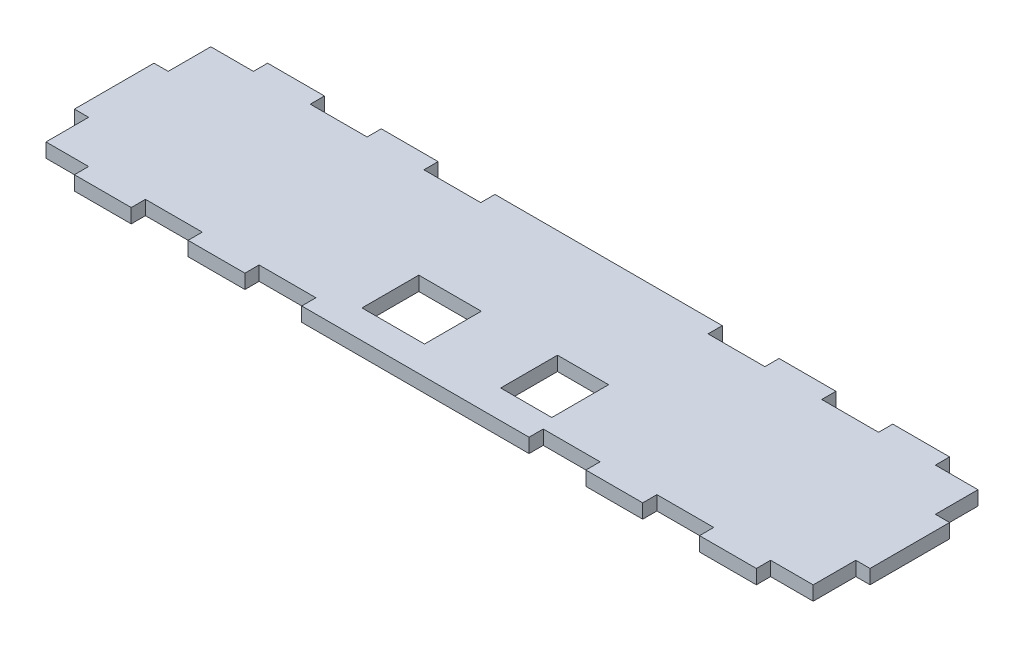
SolidWorks part; units mm, degrees
material "Acrylic (Medium-high impact)"
ref_plane "Front Plane" through (0, 0, 0) normal (0, 0, 1) x (1, 0, 0)
ref_plane "Top Plane" through (0, 0, 0) normal (0, 1, 0) x (1, 0, 0)
ref_plane "Right Plane" through (0, 0, 0) normal (1, 0, 0) x (0, 0, -1)
sketch "Sketch1" plane through (0, 0, 0) normal (0, 1, 0) x (1, 0, 0)
  line L1 (0, 0) -> (171.45, 0)
  line L2 (0, 0) -> (0, 36.83)
  line L3 (0, 36.83) -> (171.45, 36.83)
  line L4 (171.45, 0) -> (171.45, 36.83)
  dimension "D1" = 36.83
  dimension "D2" = 171.45
extrude "Boss-Extrude1" add sketch "Sketch1" along normal blind 3.175
sketch "Sketch2" plane through (0, 3.175, 0) normal (0, 1, 0) x (1, 0, 0)
  line L0 (85.725, 0) -> (85.725, -16.8439) construction
  line L1 (0, 0) -> (171.45, 0) construction
  line L2 (22.225, 0) -> (34.925, 0)
  line L3 (0, 0) -> (-3.175, 0)
  line L4 (0, 0) -> (0, -3.175)
  line L5 (0, -3.175) -> (-3.175, -3.175)
  line L6 (-3.175, 0) -> (-3.175, -3.175)
  line L7 (-3.175, 0) -> (9.525, 0)
  line L8 (-3.175, 0) -> (-3.175, -3.175)
  line L9 (-3.175, -3.175) -> (9.525, -3.175)
  line L10 (9.525, 0) -> (9.525, -3.175)
  line L11 (22.225, 0) -> (22.225, -3.175)
  line L12 (22.225, -3.175) -> (34.925, -3.175)
  line L13 (34.925, 0) -> (34.925, -3.175)
  line L14 (47.625, 0) -> (60.325, 0)
  line L15 (47.625, 0) -> (47.625, -3.175)
  line L16 (47.625, -3.175) -> (60.325, -3.175)
  line L17 (60.325, 0) -> (60.325, -3.175)
  line L18 (-3.175, -3.175) -> (174.625, -3.175)
  line L19 (85.725, -3.175) -> (85.725, 0)
  line L20 (174.625, 0) -> (-3.175, 0)
  line L21 (111.125, 0) -> (111.125, -3.175)
  line L22 (123.825, -3.175) -> (111.125, -3.175)
  line L23 (123.825, 0) -> (123.825, -3.175)
  line L24 (123.825, 0) -> (111.125, 0)
  line L25 (136.525, 0) -> (136.525, -3.175)
  line L26 (149.225, -3.175) -> (136.525, -3.175)
  line L27 (149.225, 0) -> (149.225, -3.175)
  line L28 (161.925, 0) -> (161.925, -3.175)
  line L29 (174.625, -3.175) -> (161.925, -3.175)
  line L30 (174.625, 0) -> (174.625, -3.175)
  line L31 (174.625, 0) -> (161.925, 0)
  line L32 (174.625, 0) -> (174.625, -3.175)
  line L33 (171.45, -3.175) -> (174.625, -3.175)
  line L34 (171.45, 0) -> (171.45, -3.175)
  line L35 (171.45, 0) -> (174.625, 0)
  line L36 (149.225, 0) -> (136.525, 0)
  line M3 (0, 0) -> (171.45, 0)
  dimension "D1" = 3.175
  dimension "D2" = 12.7
  dimension "D3" = 3
extrude "Boss-Extrude2" add sketch "Sketch2" against normal blind 3.175 contours L10 L18 L11 M3 | L13 L18 L15 M3 | L18 L19 L17 M3 | L21 L19 L18 M3 | L25 L23 L18 M3 | L28 L27 L18 M3 region at (15.875, 3.175, 1.5875) region at (41.275, 3.175, 1.5875) region at (73.025, 3.175, 1.5875) region at (98.425, 3.175, 1.5875) region at (130.175, 3.175, 1.5875) region at (155.575, 3.175, 1.5875)
sketch "Sketch3" plane through (0, 3.175, 0) normal (0, 1, 0) x (1, 0, 0)
  line L0 (85.725, -3.175) -> (85.725, 3.175) construction
  line L1 (60.325, -3.175) -> (111.125, -3.175) construction
  line L2 (0, 3.175) -> (171.45, 3.175) construction
  line L3 (0, 36.83) -> (0, 0) construction
  line L4 (171.45, 0) -> (171.45, 36.83) construction
  line L6 (60.325, 0) -> (67.437, 0)
  line L7 (60.325, 0) -> (60.325, 25.654)
  line L8 (60.325, 25.654) -> (67.437, 25.654)
  line L9 (67.437, 0) -> (67.437, 25.654)
  line L10 (111.125, 0) -> (109.855, 0)
  line L11 (111.125, 0) -> (111.125, 29.21)
  line L12 (111.125, 29.21) -> (109.855, 29.21)
  line L13 (109.855, 0) -> (109.855, 29.21)
  line L14 (67.437, 3.175) -> (109.855, 3.175)
  line L15 (67.437, 3.175) -> (67.437, 15.875)
  line L16 (67.437, 15.875) -> (109.855, 15.875)
  line L17 (109.855, 3.175) -> (109.855, 15.875)
  dimension "D1" = 6.35
  dimension "D2" = 7.112
  dimension "D3" = 1.27
  dimension "D4" = 12.7
extrude "Cut-Extrude1" cut sketch "Sketch3" against normal blind 3.175 contours L14 L17 L16 L15
sketch "Sketch5" plane through (0, 3.175, 0) normal (0, 1, 0) x (1, 0, 0)
  line L0 (67.437, 3.175) -> (109.855, 3.175) construction
  line L1 (67.437, 15.875) -> (81.407, 15.875)
  line L2 (67.437, 15.875) -> (67.437, 3.175)
  line L3 (67.437, 3.175) -> (81.407, 3.175)
  line L4 (81.407, 15.875) -> (81.407, 3.175)
  line L5 (67.437, 15.875) -> (109.855, 15.875) construction
  line L6 (109.855, 3.175) -> (98.425, 3.175)
  line L7 (109.855, 3.175) -> (109.855, 15.875)
  line L8 (109.855, 15.875) -> (98.425, 15.875)
  line L9 (98.425, 3.175) -> (98.425, 15.875)
  line L11 (81.407, 15.875) -> (98.425, 15.875)
  line L12 (81.407, 15.875) -> (81.407, 3.175)
  line L13 (81.407, 3.175) -> (98.425, 3.175)
  line L14 (98.425, 15.875) -> (98.425, 3.175)
  line M26 (67.437, 15.875) -> (109.855, 15.875)
  line M28 (109.855, 3.175) -> (67.437, 3.175)
  dimension "D1" = 13.97
  dimension "D2" = 11.43
extrude "Boss-Extrude3" add sketch "Sketch5" against normal blind 3.175 contours L9 L4 M28 M26 region at (89.916, 3.175, -9.525)
sketch "Sketch6" plane through (0, 3.175, 0) normal (0, 1, 0) x (1, 0, 0)
  line L0 (0, 36.83) -> (0, 0) construction
  line L1 (9.525, -3.175) -> (-3.175, -3.175)
  line L2 (9.525, -3.175) -> (9.525, 9.525)
  line L3 (9.525, 9.525) -> (-3.175, 9.525)
  line L4 (-3.175, -3.175) -> (-3.175, 9.525)
  line L5 (161.925, -3.175) -> (174.625, -3.175)
  line L6 (161.925, -3.175) -> (161.925, 9.525)
  line L7 (161.925, 9.525) -> (174.625, 9.525)
  line L8 (174.625, -3.175) -> (174.625, 9.525)
  line L9 (0, 36.83) -> (-3.175, 36.83)
  line L10 (0, 36.83) -> (0, 40.005)
  line L11 (0, 40.005) -> (-3.175, 40.005)
  line L12 (-3.175, 36.83) -> (-3.175, 40.005)
  line L13 (171.45, 36.83) -> (174.625, 36.83)
  line L14 (171.45, 36.83) -> (171.45, 40.005)
  line L15 (171.45, 40.005) -> (174.625, 40.005)
  line L16 (174.625, 36.83) -> (174.625, 40.005)
  line L17 (174.625, 40.005) -> (161.925, 40.005)
  line L18 (174.625, 40.005) -> (174.625, 27.305)
  line L19 (174.625, 27.305) -> (161.925, 27.305)
  line L20 (161.925, 40.005) -> (161.925, 27.305)
  line L21 (-3.175, 40.005) -> (9.525, 40.005)
  line L22 (-3.175, 40.005) -> (-3.175, 27.305)
  line L23 (-3.175, 27.305) -> (9.525, 27.305)
  line L24 (9.525, 40.005) -> (9.525, 27.305)
  line L25 (-3.175, 27.305) -> (0, 27.305)
  line L26 (-3.175, 27.305) -> (-3.175, 9.525)
  line L27 (-3.175, 9.525) -> (0, 9.525)
  line L28 (0, 27.305) -> (0, 9.525)
  line L29 (171.45, 0) -> (171.45, 36.83) construction
  line L30 (174.625, 27.305) -> (171.45, 27.305)
  line L31 (174.625, 27.305) -> (174.625, 9.525)
  line L32 (174.625, 9.525) -> (171.45, 9.525)
  line L33 (171.45, 27.305) -> (171.45, 9.525)
  line M5 (0, 36.83) -> (0, 0)
  line M27 (171.45, 0) -> (171.45, 36.83)
  dimension "D1" = 12.7
  dimension "D2" = 12.7
  dimension "D3" = 12.7
  dimension "D4" = 3.175
  dimension "D5" = 3.175
  dimension "D6" = 12.7
  dimension "D7" = 12.7
extrude "Boss-Extrude4" add sketch "Sketch6" against normal blind 3.175 contours L31 L19 L7 M27 | L23 L26 L3 M5 region at (-1.5875, 3.175, -18.415) region at (173.0375, 3.175, -18.415)
ref_plane "Plane2" through (0, 0, -18.415) normal (0, 0, -1) x (-1, 0, 0)
mirror "Mirror1" about plane through (0, 0, -18.415) normal (0, 0, -1) of "Boss-Extrude2"
